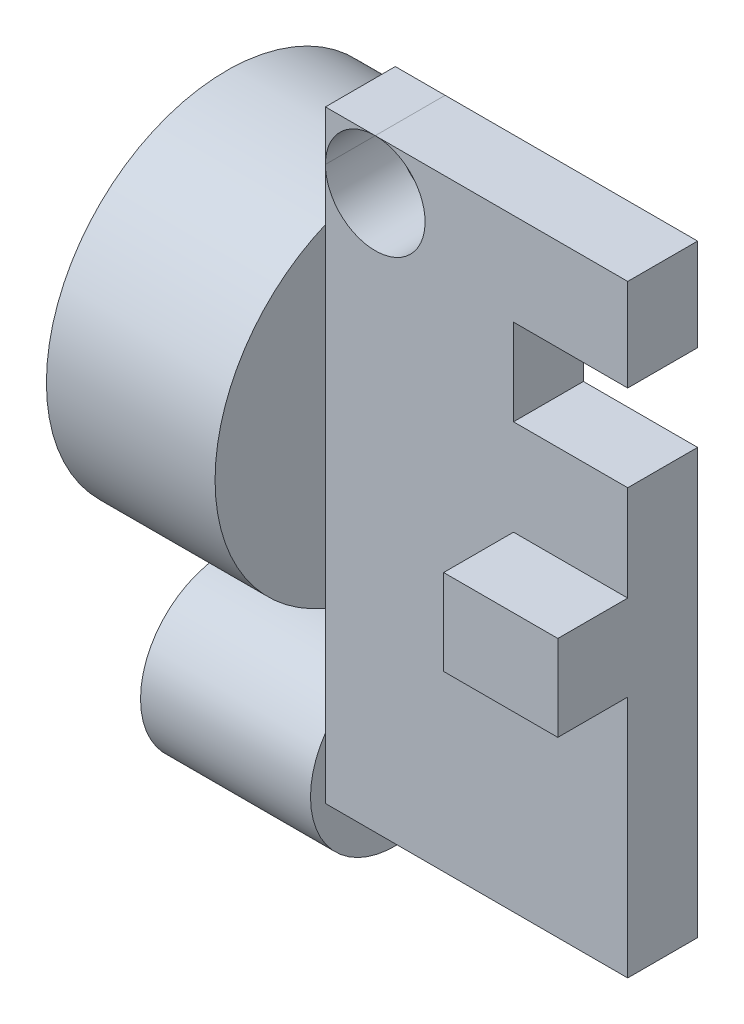
SolidWorks part; units mm, degrees
ref_plane "前视基准面" through (0, 0, 0) normal (0, 0, 1) x (1, 0, 0)
ref_plane "上视基准面" through (0, 0, 0) normal (0, 1, 0) x (1, 0, 0)
ref_plane "右视基准面" through (0, 0, 0) normal (1, 0, 0) x (0, 0, -1)
other "Configuration Table"
sketch "草图1" plane through (0, 0, 0) normal (0, 0, 1) x (1, 0, 0)
  line L1 (0, 0) -> (43.2547, 0)
  line L2 (0, 0) -> (0, 86.3197)
  line L3 (0, 86.3197) -> (43.2547, 86.3197)
  line L4 (43.2547, 0) -> (43.2547, 86.3197)
extrude "凸台-拉伸1" add sketch "草图1" along normal blind 10
sketch "草图2" plane through (0, 0, 0) normal (0, 0, 1) x (1, 0, 0)
  line L0 (0, 73.7527) -> (-24.1355, 73.7527)
  line L1 (0, 86.3197) -> (0, 0) construction
  line L2 (-24.1355, 73.7527) -> (-24.1355, 47.9637)
  line L3 (-24.1355, 47.9637) -> (0, 47.9637)
  line L4 (0, 73.7527) -> (0, 47.9637)
revolve "旋转3" add sketch "草图2" angle 360 about L3
sketch "草图3" plane through (0, 0, 0) normal (0, 0, 1) x (1, 0, 0)
  line L0 (0, 24.1924) -> (0, 0) construction
  line L2 (-24.3201, 13.9997) -> (0, 13.9997)
  line L3 (-24.3201, 13.9997) -> (-24.3201, 1.8637)
  line L4 (-24.3201, 1.8637) -> (0, 1.8637) construction
  line L5 (0, 13.9997) -> (0, 1.8637)
  line L6 (0, 1.8637) -> (-24.3201, 1.8637)
revolve "旋转5" add sketch "草图3" angle 360 about L4
sketch "草图4" plane through (0, 0, 10) normal (0, 0, 1) x (1, 0, 0)
  line L0 (43.2547, 0) -> (43.2547, 86.3197) construction
  line L1 (26.9141, 73.1059) -> (43.2547, 73.1059)
  line L2 (26.9141, 73.1059) -> (26.9141, 60.7517)
  line L3 (26.9141, 60.7517) -> (43.2547, 60.7517)
  line L4 (43.2547, 73.1059) -> (43.2547, 60.7517)
  line L6 (26.9141, 47.0772) -> (43.2547, 47.0772)
  line L7 (26.9141, 47.0772) -> (26.9141, 34.8173)
  line L8 (26.9141, 34.8173) -> (43.2547, 34.8173)
  line L9 (43.2547, 47.0772) -> (43.2547, 34.8173)
  line M6 (43.2547, 0) -> (43.2547, 86.3197)
extrude "切除-拉伸1" cut sketch "草图4" against normal blind 10 contours L2 L3 L1 M6 region at (35.0844, 66.9288, 10)
extrude "凸台-拉伸2" add sketch "草图4<3>" along normal blind 10 contours L7 L8 L6 M6 region at (35.0844, 40.9472, 10)
sketch "草图4<3>" plane through (0, 0, 10) normal (0, 0, 1) x (1, 0, 0) same geometry as "草图4"
sketch "草图8" plane through (0, 0, 10) normal (0, 0, 1) x (1, 0, 0)
  line L3 (43.2547, 86.3197) -> (0, 86.3197) construction
  line L4 (0, 86.3197) -> (0, 71.7349) construction
  circle A0 centre (7.1306, 79.189) radius 7.1306
  point P2 (9.3837, 78.6934)
extrude "切除-拉伸3" cut sketch "草图8" against normal blind 10
